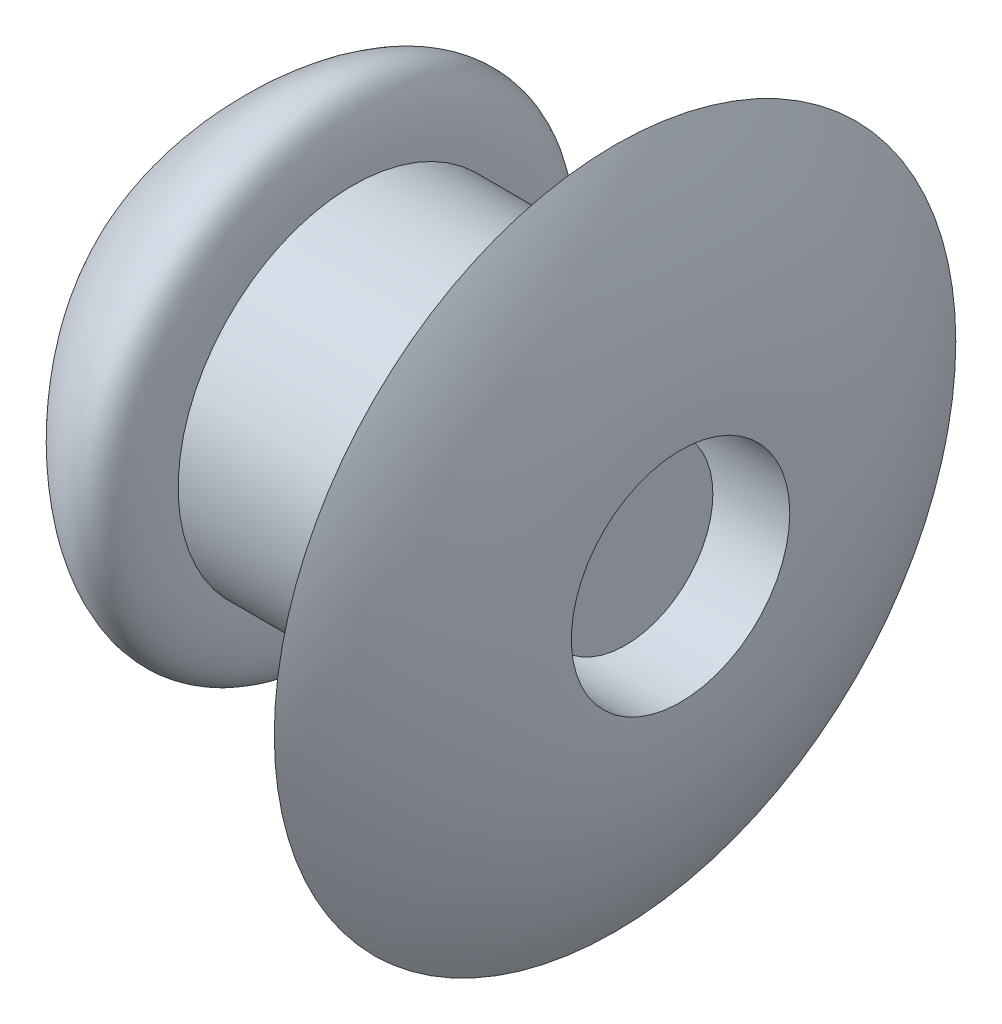
SolidWorks part; units mm, degrees
material "AISI 316 Arkusz stali nierdzewnej (SS)"
ref_plane "Płaszczyzna przednia" through (0, 0, 0) normal (0, 0, 1) x (1, 0, 0)
ref_plane "Płaszczyzna górna" through (0, 0, 0) normal (0, 1, 0) x (1, 0, 0)
ref_plane "Płaszczyzna prawa" through (0, 0, 0) normal (1, 0, 0) x (0, 0, -1)
sketch "Szkic1" plane through (0, 0, 0) normal (0, 0, 1) x (1, 0, 0)
  line L0 (350.8561, 893.6816) -> (346.1811, 893.6816)
  line L1 (351.4866, 894.9316) -> (347.7366, 894.9316)
  line L2 (347.7366, 894.9316) -> (347.7366, 894.6816)
  line L3 (347.7366, 894.6816) -> (350.8561, 894.6816)
  line L4 (350.8561, 894.6816) -> (350.8561, 893.6816)
  line L5 (350.7366, 897.5816) -> (350.7366, 895.6816)
  line L6 (350.7366, 895.6816) -> (347.7366, 895.6816)
  line L7 (350.8561, 893.6816) -> (346.1811, 893.6816) construction
  line L8 (350.8561, 893.6816) -> (346.1811, 893.6816) construction
  line L9 (351.4866, 893.6816) -> (350.8561, 893.6816) construction
  line L10 (350.7366, 521.1816) -> (350.7366, 901.1816) construction
  line L14 (347.7366, 938.0684) -> (347.7366, 617.45) construction
  arc A0 (351.4866, 894.9316) -> (350.7366, 897.5816) centre (346.4299, 894.9316) ccw
  spline S0 degree 3 poles (347.7366, 895.6816) (347.7732, 898.0214) (344.2732, 893.3094) (346.4953, 895.1701) (346.792, 894.8565) knots 0 0 0 0 0.744502 1 1 1 1
  spline S1 degree 2 poles (346.792, 894.8565) (345.909, 894.8746) (346.1811, 893.6816) knots 0 0 0 1 1 1
  point P4 (0, 0)
  point P5 (347.6551, 895.6816)
  point P8 (0, 0)
  point P12 (0, 0)
  dimension "D1" = 2
  dimension "D2" = 0.1195
  dimension "D3" = 4
  dimension "D4" = 2.5
  dimension "D5" = 0.75
  dimension "D6" = 7.8
  dimension "D7" = 0.9668
  dimension "D8" = 1.1117
  dimension "D9" = 1.175
  dimension "D10" = 1.2811
  dimension "D11" = 2.7999
  dimension "D12" = 0.4548
  dimension "D13" = 0.9446
  dimension "D14" = 1.1893
  dimension "D15" = 1.3067
  dimension "D16" = 2.0033
  dimension "D17" = 1.5555
revolve "Obrót1" add sketch "Szkic1" angle 360 about L7
